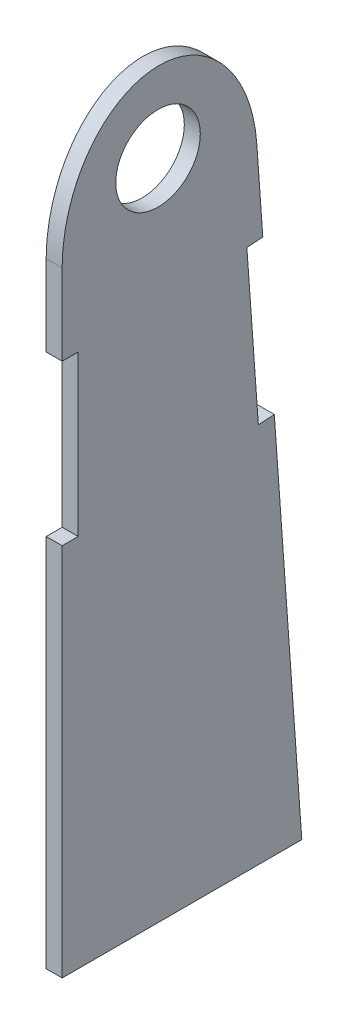
SolidWorks part; units mm, degrees
material "AISI 4130 Steel, annealed at 865C"
ref_plane "X-Y Datum" through (0, 0, 0) normal (0, 0, 1) x (1, 0, 0)
ref_plane "X-Z Datum" through (0, 0, 0) normal (0, 1, 0) x (1, 0, 0)
ref_plane "Y-Z Datum" through (0, 0, 0) normal (1, 0, 0) x (0, 0, -1)
sketch "Sketch1" plane through (0, 0, 0) normal (1, 0, 0) x (0, 0, -1)
  line L0 (0, -65.7746) -> (-9.525, -65.7746)
  line L1 (-9.525, -65.7746) -> (-9.525, 0)
  line L2 (0, -65.7746) -> (14.2875, -65.7746)
  line L3 (14.2875, -65.7746) -> (9.5004, 0.6843)
  line L4 (0, -65.7746) -> (0, 0) construction
  line L5 (-9.525, -28.575) -> (-7.9375, -28.575)
  line L10 (-9.525, -28.575) -> (-9.525, -12.7)
  line L11 (-7.9375, -28.575) -> (-7.9375, -12.7)
  line L12 (-9.525, -12.7) -> (-7.9375, -12.7)
  line L13 (11.5534, -27.8168) -> (10.4128, -11.9829)
  line L14 (11.5534, -27.8168) -> (9.97, -27.9309)
  line L15 (10.4128, -11.9829) -> (8.8294, -12.0969)
  line L16 (9.97, -27.9309) -> (8.8294, -12.0969)
  arc A0 (9.5004, 0.6843) -> (-9.525, 0) centre (0, 0) ccw
  dimension "D1" = 9.525
  dimension "D2" = 14.2875
  dimension "D3" = 9.525
  dimension "D4" = 65.7746
  dimension "D5" = 1.5875
  dimension "D6" = 15.875
  dimension "D7" = 12.7
  dimension "D8" = 12.7
extrude "Boss-Extrude1" add sketch "Sketch1" along normal blind 1.5875 contours L3 A0 L1 L12 L11 L5 L0 L2 L14 L16 L15 region at (0, -30.9437, -1.1399)
hole_wizard "M8 Clearance Hole1" positions "Sketch2" profile "Sketch3" hole size "M8" standard "ANSI Metric" end condition through all
sketch "Sketch2" plane through (1.5875, 0, 0) normal (1, 0, 0) x (0, 0, -1)
  point P0 (0, 0)
sketch "Sketch3" plane through (1.5875, 0, 0) normal (0, 1, 0) x (0, 0, -1)
  line L0 (0, 0) -> (0, 1.5875)
  line L1 (0, 1.5875) -> (4.2, 1.5875)
  line L2 (4.2, 1.5875) -> (4.2, 0)
  line L5 (4.2, 0) -> (0, 0)
  line L11 (0, -6.35) -> (0, 107.95) construction
  dimension "Thru Hole Dia." = 8.4
  dimension "Thru Hole Depth" = 1.5875
sketch "Sketch4" plane through (1.5875, 0, 0) normal (1, 0, 0) x (0, 0, -1)
  line L2 (10.4128, -11.9829) -> (9.5004, 0.6843) construction
  line L3 (-9.525, -12.7) -> (-9.525, 0) construction
  line L5 (9.8132, -3.6584) -> (9.5004, 0.6843)
  line L6 (-9.525, -4.6718) -> (-9.525, 0)
  arc A3 (9.5004, 0.6843) -> (-9.525, 0) centre (0, 0) ccw construction
  arc A4 (9.5004, 0.6843) -> (-9.525, 0) centre (0, 0) ccw
  ellipse E0 centre (0.1656, -4.7625) end of major axis (0.3311, -17.4625) minor radius 9.69 (9.8132, -3.6584) -> (-9.525, -4.6718) ccw
  point P7 (0, 7.9375)
  arc M5 (9.5004, 0.6843) -> (-9.525, 0) centre (0, 0) ccw
  dimension "D1" = 7.9375
  dimension "D2" = 4.7625
extrude "Cut-Extrude1" cut sketch "Sketch4" against normal through all contours M5 region at (1.5875, 8.1621, 0.3961)
equation "\"D8@Sketch1\"=\"D7@Sketch1\""
